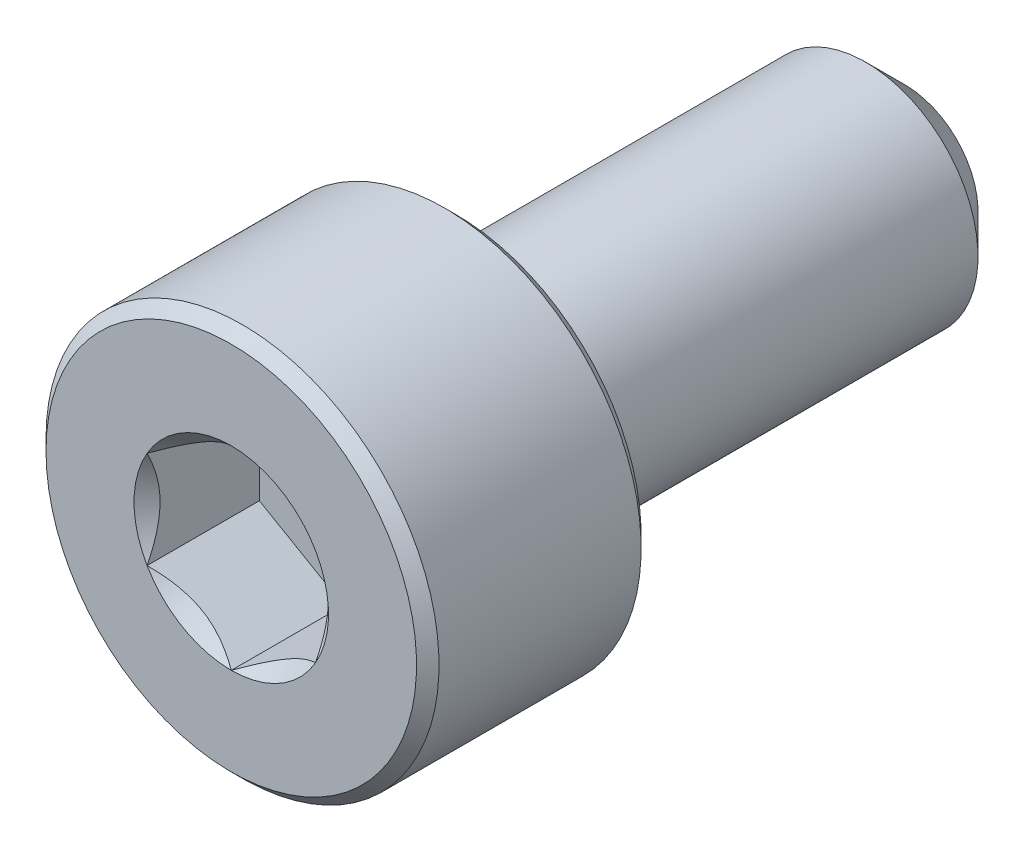
SolidWorks part; units mm, degrees
material "Alloy Steel"
ref_plane "Front Plane" through (0, 0, 0) normal (0, 0, 1) x (1, 0, 0)
ref_plane "Top Plane" through (0, 0, 0) normal (0, 1, 0) x (1, 0, 0)
ref_plane "Right Plane" through (0, 0, 0) normal (1, 0, 0) x (0, 0, -1)
sketch "Sketch1" plane through (0, 0, 0) normal (1, 0, 0) x (0, 0, -1)
  line L0 (-6, 0) -> (6, 0) construction
  line L1 (6, 0) -> (6, 1.3) construction
  line L2 (6, 1.3) -> (5.3, 2) construction
  line L3 (5.3, 2) -> (-2, 2) construction
  line L5 (-2, 2) -> (-2, 3.5) construction
  line L6 (-2, 3.5) -> (-6, 3.5) construction
  line L7 (-6, 3.5) -> (-6, 0) construction
  line L8 (6, 1.3) -> (6, 2) construction
  line L9 (5.9563, 2.0758) -> (6.3063, 1.4696) construction
  line L10 (6.3063, 1.4696) -> (6.6563, 2.0758) construction
  line L11 (6.6563, 2.0758) -> (5.9563, 2.0758) construction
  line L12 (6.3063, 2.0758) -> (6.3063, 2) construction
  line L13 (6.3063, 1.4696) -> (6.3063, 1.5453) construction
  line L14 (6.2625, 1.5453) -> (6.35, 1.5453) construction
  line L15 (6, 2) -> (6.6125, 2) construction
  line L16 (5.9781, 2.0379) -> (6.6344, 2.0379) construction
  line L17 (6, 0) -> (6, -2) construction
  line L18 (-2.2, 3.5) -> (-2, 3.3) construction
  line L19 (-5.8, 3.5) -> (-6, 3.3) construction
  point P0 (-6, 1.5)
  point P3 (3.55, 2)
  point P4 (0, 0)
  point P22 (6.3063, 1.5453)
  point P24 (-2, 2)
  point P25 (6.3063, 2)
  point P28 (6.3063, 2.0379)
  point P29 (3.55, -2)
  point P31 (-4, 3.5)
  point P37 (-2.7, 3.5)
  point P38 (-5.7, 3.5)
  point P41 (-4, 0)
  dimension "head height" = 4
  dimension "D1" = 45
  dimension "Head Diameter" = 7
  dimension "Thread Size" = 4
  dimension "drive size" = 3
  dimension "Thread Pitch" = 0.7
  dimension "D2" = 0.0875
  dimension "D3" = 0.7
  dimension "D4" = 2.45
  dimension "D7" = 0.2
  dimension "D8" = 0.2
  dimension "D9" = 0.2
  dimension "D10" = 0.1
  dimension "D11" = 0.5
  dimension "length" = 8
  dimension "Drive Depth" = 2
sketch "Sketch2" plane through (0, 0, 0) normal (1, 0, 0) x (0, 0, -1)
  line L1 (-5.8, 3.5) -> (-2.2, 3.5)
  line L4 (5.3, 2) -> (6, 1.3)
  line L5 (6, 1.3) -> (6, 0)
  line L6 (-2.2, 3.5) -> (-2, 3.3) construction
  line L7 (6, 0) -> (-6, 0)
  line L8 (-5.8, 3.5) -> (-6, 3.3) construction
  line L9 (-2.2, 3.5) -> (-2, 3.3)
  line L10 (-5.8, 3.5) -> (-6, 3.3)
  line L11 (-6, 3.3) -> (-6, 0)
  line L12 (-2, 3.3) -> (-2, 2)
  line L13 (-2, 2) -> (5.3, 2)
revolve "Revolve1" add sketch "Sketch2" angle 360 about L7
sketch "Sketch3" plane through (0, 0, 6) normal (0, 0, 1) x (1, 0, 0)
  line L1 (0, 1.7321) -> (-1.5, 0.866)
  line L2 (-1.5, 0.866) -> (-1.5, -0.866)
  line L3 (-1.5, -0.866) -> (0, -1.7321)
  line L4 (0, -1.7321) -> (1.5, -0.866)
  line L5 (1.5, -0.866) -> (1.5, 0.866)
  line L6 (1.5, 0.866) -> (0, 1.7321)
  circle A0 centre (0, 0) radius 1.5 construction
  dimension "D1" = 3
extrude "Cut-Extrude1" cut sketch "Sketch3" against normal up to vertex (2 mm away) up to point (0, 0, 4)
sketch "Sketch4" plane through (0, 0, 6) normal (0, 0, 1) x (1, 0, 0)
  circle A0 centre (0, 0) radius 1.7321
extrude "Cut-Extrude2" cut sketch "Sketch4" against normal blind 0.5 draft 45
ref_plane "Plane1" [suppressed] through (0, 0, 2) normal (0, 0, 1) x (1, 0, 0)
split "Split1" [suppressed] bodies to split 106
sketch "Sketch6" [suppressed] plane through (0, 0, -6) normal (0, 0, -1) x (-1, 0, 0)
  circle A0 centre (0, 0) radius 2
curve "Helix/Spiral1" [suppressed] pitch 0.7 height 8.7 turns 12.4286
sketch "Sketch7" [suppressed] plane through (0, 0, 0) normal (1, 0, 0) x (0, 0, -1)
  line L0 (5.9781, 2.0379) -> (6.6344, 2.0379)
  line L1 (6.6344, 2.0379) -> (6.35, 1.5453)
  line L2 (6.35, 1.5453) -> (6.2625, 1.5453)
  line L3 (6.2625, 1.5453) -> (5.9781, 2.0379)
sweep "Cut-Sweep1" [suppressed] cut profiles "Sketch7" path "Helix/Spiral1"
sketch "Sketch8" [suppressed] plane through (0, 0, 2) normal (0, 0, -1) x (-1, 0, 0)
  circle A0 centre (0, 0) radius 2
extrude "Boss-Extrude1" [suppressed] add sketch "Sketch8" along normal through all draft 45
ref_plane "Plane2" [suppressed] through (0, 0, 4) normal (0, 0, 1) x (1, 0, 0)
sketch "Sketch9" [suppressed] plane through (0, 0, 4) normal (0, 0, 1) x (1, 0, 0)
  line L0 (0, 3.4038) -> (0.0916, 3.4988)
  line L1 (0, 3.4038) -> (-0.0916, 3.4988)
  line L2 (0, 3.5) -> (0, 0) construction
  line L3 (-0.0916, 3.4988) -> (0, 0) construction
  line L4 (0, 0) -> (0.0916, 3.4988) construction
  arc A0 (0.0916, 3.4988) -> (-0.0916, 3.4988) centre (0, 0) ccw
  circle A1 centre (0, 0) radius 3.4038 construction
  dimension "D1" = 7
  dimension "D2" = 6.8075
  dimension "D3" = 3
extrude "Cut-Extrude4" [suppressed] cut sketch "Sketch9" against normal up to vertex and the other way up to vertex
pattern_circular "CirPattern2" [suppressed] count 96 over 360 about axis through (0, 0, 6) along (0, 0, -1) of bodies 113
equation "\"D2@Sketch1\" = \"Thread Pitch@Sketch1\" / 8"
equation "\"D3@Sketch1\" = \"Thread Pitch@Sketch1\""
equation "\"D3@Helix/Spiral1\" = \"length@Sketch1\" + \"Thread Pitch@Sketch1\""
equation "\"D4@Helix/Spiral1\" = \"Thread Pitch@Sketch1\""
equation "\"D4@Sketch1\" = \"Thread Pitch@Sketch1\" * 3.5"
equation "\"D7@Sketch1\"=\"head height@Sketch1\"*.05"
equation "\"D8@Sketch1\"=\"D7@Sketch1\""
equation "\"D9@Sketch1\"=\"D7@Sketch1\""
equation "\"D10@Sketch1\"=\"D7@Sketch1\"/2"
equation "\"D11@Sketch1\"=\"D10@Sketch1\"*5"
equation "\"D1@CirPattern2\"=( 360 / \"D3@Sketch9\" )*0.8"
equation "\"D1@Sketch3\" = \"drive size@Sketch1\""
equation "\"D2@Sketch9\"=\"Head Diameter@Sketch1\" * 0.9725"
